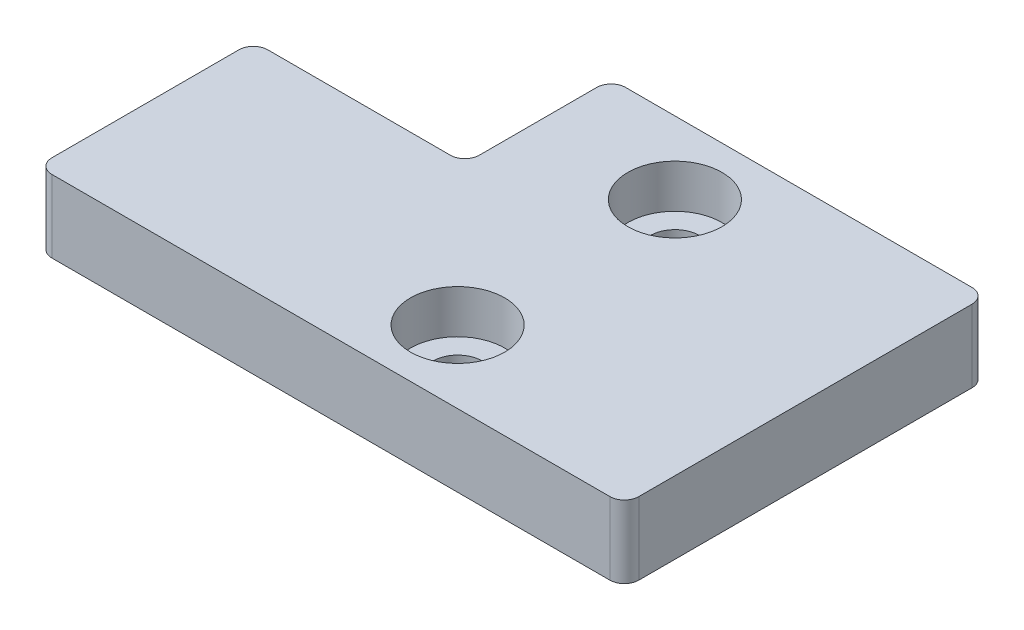
SolidWorks part; units mm, degrees
ref_plane "Front Plane" through (0, 0, 0) normal (0, 0, 1) x (1, 0, 0)
ref_plane "Top Plane" through (0, 0, 0) normal (0, 1, 0) x (1, 0, 0)
ref_plane "Right Plane" through (0, 0, 0) normal (1, 0, 0) x (0, 0, -1)
sketch "Sketch1" plane through (0, 0, 0) normal (0, 1, 0) x (1, 0, 0)
  line L0 (0, 0) -> (40.51, 0)
  line L1 (40.51, 0) -> (40.51, 25)
  line L2 (40.51, 25) -> (14.6, 25)
  line L3 (14.6, 25) -> (14.6, 14.9)
  line L4 (14.6, 14.9) -> (0, 14.9)
  line L5 (0, 14.9) -> (0, 0)
  dimension "D1" = 40.51
  dimension "D2" = 25
  dimension "D3" = 14.6
  dimension "D4" = 10.1
extrude "Boss-Extrude1" add sketch "Sketch1" along normal blind 5
fillet "Fillet1" radius 1 6 edges at (0, 2.5, -14.9) (14.6, 2.5, -14.9) (14.6, 2.5, -25) (40.51, 2.5, -25) (40.51, 2.5, 0) (0, 2.5, 0)
sketch "Sketch2" plane through (0, 5, 0) normal (0, 1, 0) x (1, 0, 0)
  line L0 (24, 25) -> (24, 0) construction
  line L1 (39.51, 25) -> (15.6, 25) construction
  line L2 (1, 0) -> (39.51, 0) construction
  line L3 (40.51, 1) -> (40.51, 24) construction
  line L4 (40.51, 12.5) -> (0, 12.5) construction
  line L5 (0, 13.9) -> (0, 1) construction
  point P12 (24, 20)
  point P13 (24, 5)
  point P14 (24, 12.5)
  dimension "D1" = 16.51
  dimension "D2" = 15
  dimension "D3" = 7.5
hole_wizard "CBORE for M3 SHCS1" positions "Sketch3" profile "Sketch4" counterbore size "M3" standard "ANSI Metric" end condition up to next
sketch "Sketch3" plane through (0, 5, 0) normal (0, 1, 0) x (1, 0, 0)
  point P0 (24, 20)
  point P3 (24, 5)
sketch "Sketch4" plane through (24, 5, -20) normal (1, 0, 0) x (0, 0, 1)
  line L0 (0, 0) -> (0, 5)
  line L1 (0, 5) -> (1.7, 5)
  line L3 (1.7, 5) -> (1.7, 3)
  line L4 (1.7, 3) -> (3.25, 3)
  line L5 (3.25, 3) -> (3.25, 0)
  line L7 (3.25, 0) -> (0, 0)
  line L11 (0, -6.35) -> (0, 107.95) construction
  dimension "Thru Hole Dia." = 3.4
  dimension "Thru Hole Depth" = 5
  dimension "C'Bore Dia." = 6.5
  dimension "C'Bore Depth" = 3
